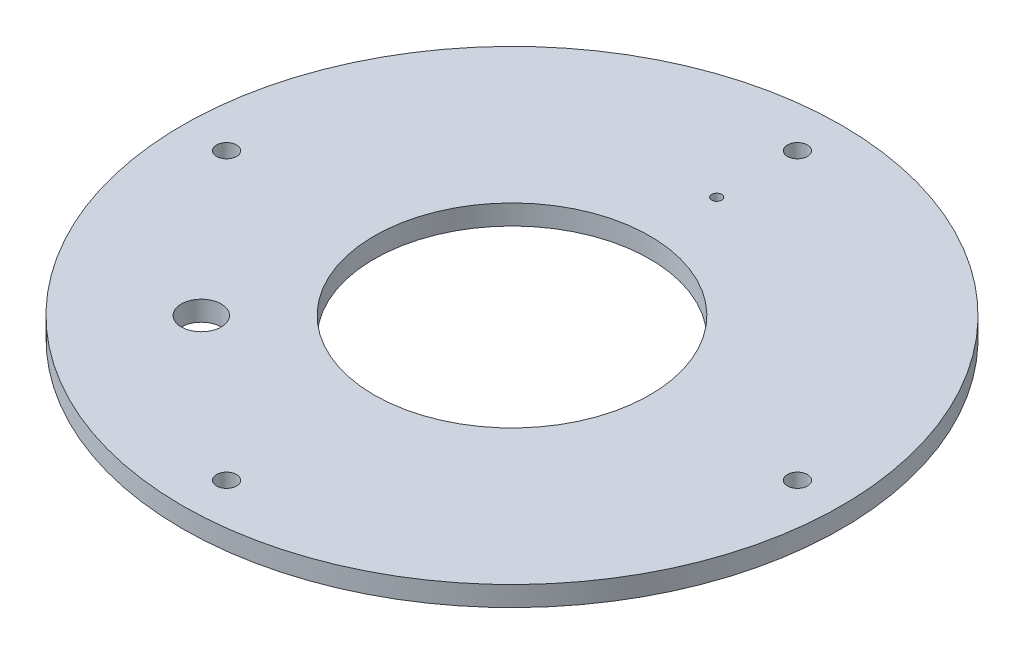
SolidWorks part; units mm, degrees
material "1060 Alloy"
ref_plane "Front Plane" through (0, 0, 0) normal (0, 0, 1) x (1, 0, 0)
ref_plane "Top Plane" through (0, 0, 0) normal (0, 1, 0) x (1, 0, 0)
ref_plane "Right Plane" through (0, 0, 0) normal (1, 0, 0) x (0, 0, -1)
sketch "Sketch1" plane through (0, 0, 0) normal (0, 1, 0) x (1, 0, 0)
  circle A0 centre (0, 0) radius 16.5
  circle A1 centre (0, 0) radius 6.9
  dimension "D1" = 33
  dimension "D2" = 13.8
extrude "Boss-Extrude1" add sketch "Sketch1" along normal blind 1
hole_wizard "CSK for M2 Flat Head Machine Screw1" positions "Sketch2" profile "Sketch3" countersink size "M2" standard "ANSI Metric" end condition through all
sketch "Sketch2" plane through (0, 0, 0) normal (0, -1, 0) x (-1, 0, 0)
  point P0 (0, -14.29)
  point P2 (-14.29, 0)
  point P4 (0, 14.29)
  point P28 (14.29, 0)
  dimension "D1" = 14.29
  dimension "D2" = 14.29
  dimension "D3" = 14.29
  dimension "D4" = 14.29
sketch "Sketch3" plane through (0, 0, 14.29) normal (1, 0, 0) x (0, 0, -1)
  line L0 (0, 0) -> (0, 1)
  line L1 (0, 1) -> (0.5, 1)
  line L2 (0.5, 1) -> (0.5, 0.2517)
  line L3 (0.5, 0.2517) -> (0.8, 0)
  line L5 (0.8, 0) -> (0, 0)
  line L6 (-0.5, 0.2517) -> (-0.8, 0) construction
  line L11 (0, -6.35) -> (0, 107.95) construction
  dimension "Thru Hole Dia." = 1
  dimension "Thru Hole Depth" = 1
  dimension "Near C'Sink Dia." = 1.6
  dimension "Near C'Sink Angle" = 100
sketch "Sketch4" plane through (0, 1, 0) normal (0, 1, 0) x (1, 0, 0)
  line L0 (0, 0) -> (-13.4332, -13.4332) construction
  circle A0 centre (0, 10.25) radius 0.25
  circle A1 centre (-7.7782, -7.7782) radius 1
  dimension "D1" = 0.5
  dimension "D2" = 10.25
  dimension "D4" = 2
  dimension "D3" = 11
  dimension "D5" = 0
extrude "Cut-Extrude1" cut sketch "Sketch4" against normal through all both and the other way through all
